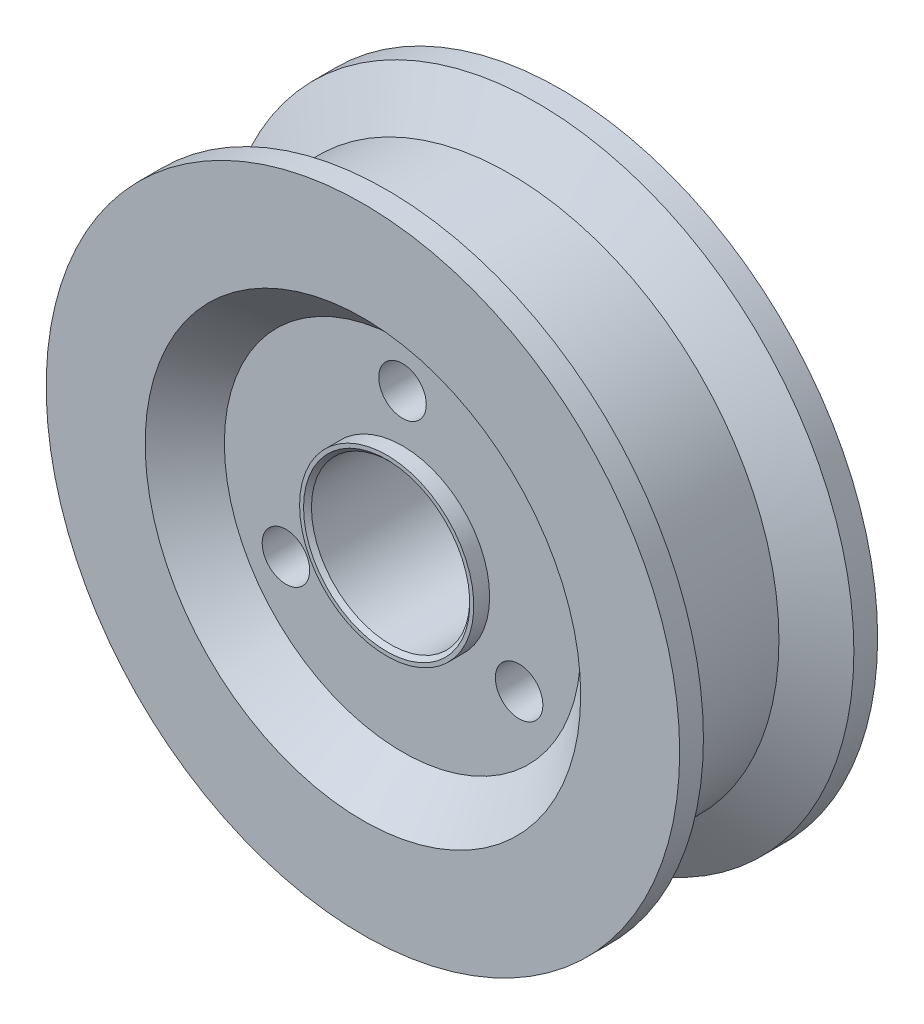
SolidWorks part; units mm, degrees
ref_plane "Plan de face" through (0, 0, 0) normal (0, 0, 1) x (1, 0, 0)
ref_plane "Plan de dessus" through (0, 0, 0) normal (0, 1, 0) x (1, 0, 0)
ref_plane "Plan de droite" through (0, 0, 0) normal (1, 0, 0) x (0, 0, -1)
sketch "Esquisse1" plane through (0, 0, 0) normal (0, 0, 1) x (1, 0, 0)
  circle A0 centre (0, 0) radius 40
  circle A1 centre (0, 0) radius 10
  dimension "D1" = 80
  dimension "D2" = 20
extrude "Boss.-Extru.1" add sketch "Esquisse1" along normal mid plane 25
sketch "Esquisse2" plane through (0, 0, 12.5) normal (0, 0, 1) x (1, 0, 0)
  circle A0 centre (0, 0) radius 22.5
  dimension "D1" = 45
extrude "Enlèv. mat.-Extru.1" cut sketch "Esquisse2" against normal blind 5
mirror "Symétrie1" about plane through (0, 0, 0) normal (0, 0, 1) of "Enlèv. mat.-Extru.1"
sketch "Esquisse3" plane through (0, 0, 0) normal (0, 1, 0) x (1, 0, 0)
  line L0 (0, 0) -> (0, 24.5385) construction
  line L1 (40, 9.5) -> (34, 6.0359)
  line L2 (40, -12.5) -> (40, 12.5) construction
  line L3 (34, 6.0359) -> (34, -6.0359)
  line L4 (34, -6.0359) -> (40, -9.5)
  line L5 (40, -9.5) -> (40, 9.5)
  line L6 (40, 12.5) -> (-40, 12.5) construction
  line L7 (-40, -12.5) -> (40, -12.5) construction
  dimension "D1" = 6
  dimension "D2" = 3
  dimension "D3" = 60
  dimension "D4" = 3
revolve "Enlèvement de matière-Révolution1" cut sketch "Esquisse3" angle 360 about L0
chamfer "Chanfrein1" distance 5 angle 45 2 edges at (22.5, 0, 12.5) (22.5, 0, -12.5)
sketch "Esquisse4" plane through (0, 0, -7.5) normal (0, 0, -1) x (-1, 0, 0)
  line L0 (0, 17) -> (0, 0) construction
  line L1 (0, 0) -> (-14.7224, -8.5) construction
  line L2 (0, 0) -> (14.7224, -8.5) construction
  circle A0 centre (0, 0) radius 17 construction
  circle A1 centre (0, 17) radius 3
  circle A2 centre (14.7224, -8.5) radius 3
  circle A3 centre (-14.7224, -8.5) radius 3
  point P11 (0, 0)
  dimension "D1" = 34
  dimension "D2" = 6
  dimension "D4" = 120
  dimension "D5" = 120
  dimension "D3" = 3
extrude "Enlèv. mat.-Extru.2" cut sketch "Esquisse4" against normal through all
sketch "Esquisse5" plane through (0, 0, -7.5) normal (0, 0, -1) x (-1, 0, 0)
  circle A0 centre (0, 0) radius 10 construction
  circle A1 centre (0, 0) radius 10
  circle A2 centre (0, 0) radius 11
  dimension "D1" = 1
extrude "Boss.-Extru.2" add sketch "Esquisse5" along normal blind 2 and the other way blind 17
chamfer "Chanfrein2" distance 0.5 angle 45 2 edges at (-10, 0, 9.5) (-10, 0, -9.5)
scale "Escala1" scale about origin uniform scaling yes scale factor 0.7916
